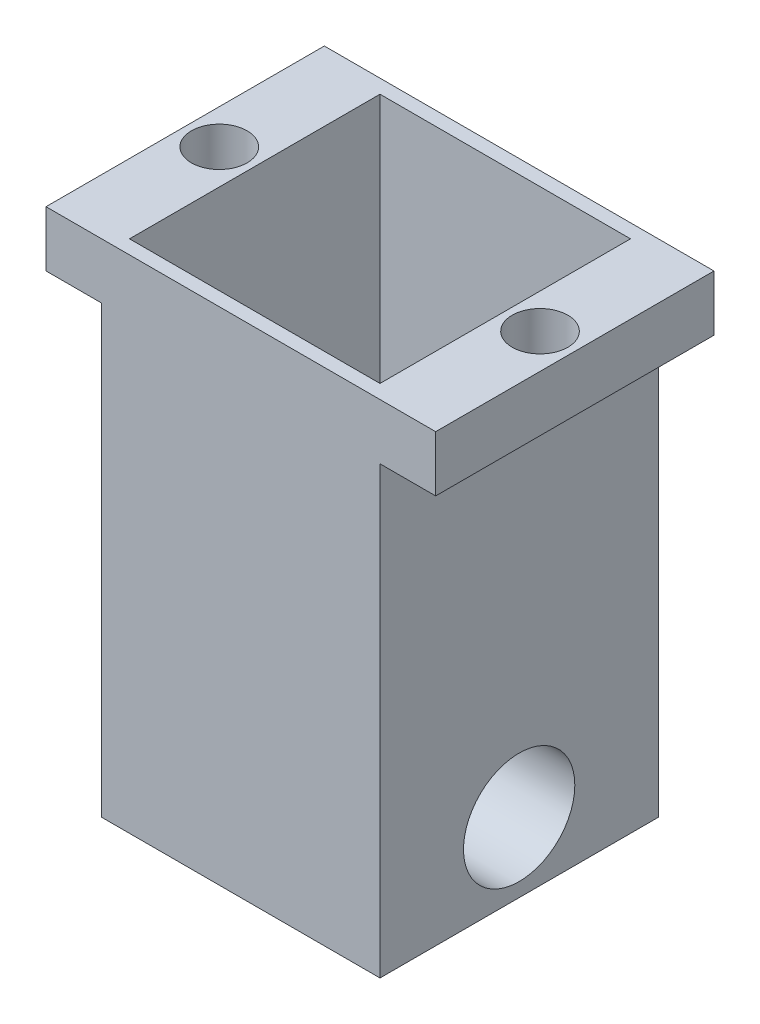
SolidWorks part; units mm, degrees
ref_plane "Front Plane" through (0, 0, 0) normal (0, 0, 1) x (1, 0, 0)
ref_plane "Top Plane" through (0, 0, 0) normal (0, 1, 0) x (1, 0, 0)
ref_plane "Right Plane" through (0, 0, 0) normal (1, 0, 0) x (0, 0, -1)
sketch "Sketch1" plane through (0, 0, 0) normal (0, 1, 0) x (1, 0, 0)
  line L1 (0, 0) -> (63.5, 0)
  line L2 (0, 0) -> (0, 63.5)
  line L3 (0, 63.5) -> (63.5, 63.5)
  line L4 (63.5, 0) -> (63.5, 63.5)
  dimension "D1" = 63.5
  dimension "D2" = 63.5
extrude "Boss-Extrude1" add sketch "Sketch1" along normal blind 31.75
sketch "Sketch2" plane through (0, 31.75, 0) normal (0, 1, 0) x (1, 0, 0)
  line L1 (0, 0) -> (63.5, 0)
  line L2 (0, 0) -> (0, 63.5)
  line L3 (0, 63.5) -> (63.5, 63.5)
  line L4 (63.5, 0) -> (63.5, 63.5)
  line L5 (3.175, 3.175) -> (60.325, 3.175)
  line L6 (3.175, 3.175) -> (3.175, 60.325)
  line L7 (3.175, 60.325) -> (60.325, 60.325)
  line L8 (60.325, 3.175) -> (60.325, 60.325)
  dimension "D1" = 3.175
  dimension "D2" = 3.175
  dimension "D3" = 3.175
  dimension "D4" = 3.175
extrude "Boss-Extrude2" add sketch "Sketch2" along normal blind 82.55
sketch "Sketch3" plane through (63.5, 0, 0) normal (1, 0, 0) x (0, 0, -1)
  line L0 (63.5, 114.3) -> (63.5, 0) construction
  line L1 (0, 114.3) -> (63.5, 114.3)
  line L2 (0, 114.3) -> (0, 101.6)
  line L3 (0, 101.6) -> (63.5, 101.6)
  line L4 (63.5, 114.3) -> (63.5, 101.6)
  dimension "D1" = 12.7
extrude "Boss-Extrude3" add sketch "Sketch3" along normal blind 12.7
ref_plane "Plane1" through (31.75, 0, 0) normal (1, 0, 0) x (0, 0, -1)
mirror "Mirror2" about plane through (31.75, 0, 0) normal (1, 0, 0) of "Boss-Extrude3"
hole_wizard "1 (1) Diameter Hole2" positions "Sketch4" profile "Sketch5" hole size "1" standard "ANSI Inch" end condition up to next
sketch "Sketch4" plane through (63.5, 0, 0) normal (1, 0, 0) x (0, 0, -1)
  line L0 (0, 0) -> (63.5, 0) construction
  point P0 (31.75, 15.875)
  point P7 (31.75, 0)
  dimension "D1" = 15.875
sketch "Sketch5" plane through (63.5, 15.875, -31.75) normal (0, 1, 0) x (0, 0, -1)
  line L0 (0, 0) -> (0, 63.5)
  line L1 (0, 63.5) -> (12.7, 63.5)
  line L2 (12.7, 63.5) -> (12.7, 0)
  line L5 (12.7, 0) -> (0, 0)
  line L11 (0, -6.35) -> (0, 107.95) construction
  dimension "Thru Hole Dia." = 25.4
  dimension "Thru Hole Depth" = 63.5
hole_wizard "1/2 (0.5) Diameter Hole1" positions "Sketch6" profile "Sketch7" hole size "1/2" standard "ANSI Inch" end condition up to next
sketch "Sketch6" plane through (0, 114.3, 0) normal (0, 1, 0) x (1, 0, 0)
  line L0 (76.2, 63.5) -> (76.2, 0) construction
  line L1 (31.75, -34.925) -> (31.75, 34.925) construction
  point P0 (68.2625, 31.75)
  point P2 (-4.7625, 31.5933)
  point P5 (0, 0)
  point P8 (76.2, 31.75)
  point P9 (0, 0)
  point P12 (0, 0)
  dimension "D1" = 73.025
  dimension "D2" = 36.5125
sketch "Sketch7" plane through (68.2625, 114.3, -31.75) normal (1, 0, 0) x (0, 0, 1)
  line L0 (0, 0) -> (0, 12.7)
  line L1 (0, 12.7) -> (6.35, 12.7)
  line L2 (6.35, 12.7) -> (6.35, 0)
  line L5 (6.35, 0) -> (0, 0)
  line L11 (0, -6.35) -> (0, 107.95) construction
  dimension "Thru Hole Dia." = 12.7
  dimension "Thru Hole Depth" = 12.7
